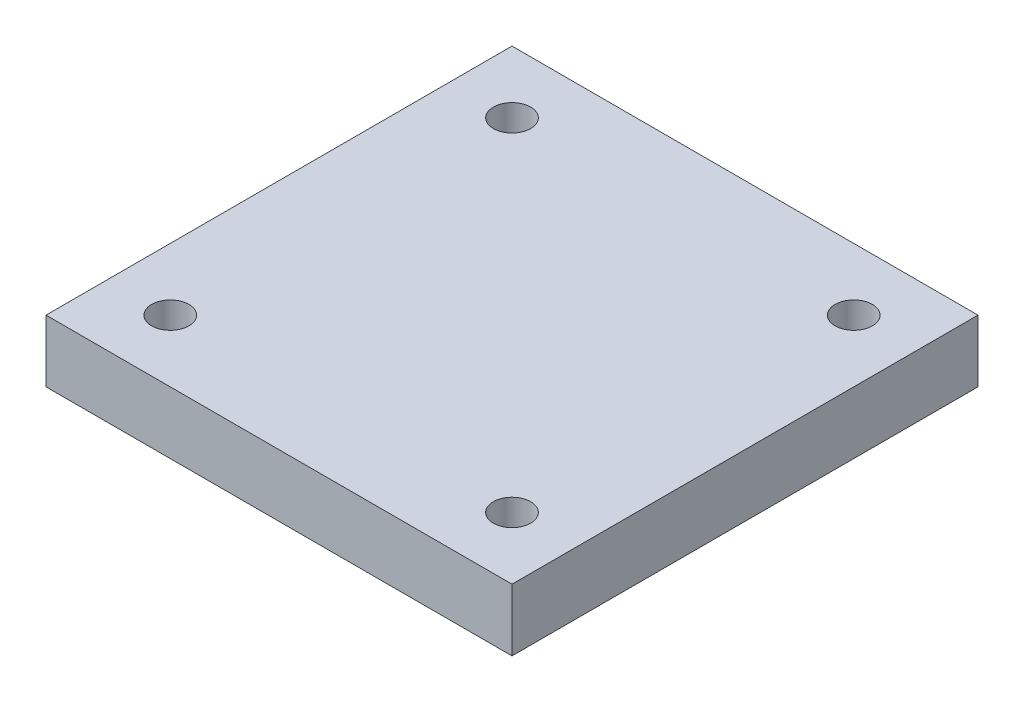
SolidWorks part; units mm, degrees
ref_plane "Front Plane" through (0, 0, 0) normal (0, 0, 1) x (1, 0, 0)
ref_plane "Top Plane" through (0, 0, 0) normal (0, 1, 0) x (1, 0, 0)
ref_plane "Right Plane" through (0, 0, 0) normal (1, 0, 0) x (0, 0, -1)
sketch "Sketch1" plane through (0, 0, 0) normal (0, 1, 0) x (1, 0, 0)
  line L1 (75, 75) -> (-75, 75)
  line L2 (75, 75) -> (75, -75)
  line L3 (75, -75) -> (-75, -75)
  line L4 (-75, 75) -> (-75, -75)
  line L5 (75, 75) -> (-75, -75) construction
  line L6 (75, -75) -> (-75, 75) construction
  point P0 (0, 0)
  dimension "D1" = 150
  dimension "D2" = 150
extrude "Boss-Extrude1" add sketch "Sketch1" along normal blind 20 contours L1 L4 L3 L2
sketch "Sketch2" plane through (0, 20, 0) normal (0, 1, 0) x (1, 0, 0)
  point P0 (55, 55)
  point P1 (55, -55)
  point P2 (-55, -55)
  point P3 (-55, 55)
  point P4 (0, 0)
  point P5 (0, 0)
  point P7 (0, 0)
  point P8 (0, 0)
  point P9 (0, 0)
  point P10 (0, 0)
  point P11 (0, 0)
  dimension "D1" = 110
  dimension "D2" = 55
  dimension "D3" = 55
  dimension "D4" = 55
hole_wizard "Ø12.0mm Dowel Hole1" positions "3DSketch1" profile "Sketch3" hole size "Ø12.0" standard "ANSI Metric" end condition up to next
sketch3d "3DSketch1"
  point P0 (55, 20, -55)
  point P3 (55, 20, 55)
  point P6 (-55, 20, 55)
  point P9 (-55, 20, -55)
sketch "Sketch3" plane through (55, 20, -55) normal (1, 0, 0) x (0, 0, 1)
  line L0 (0, 0) -> (0, 20)
  line L1 (0, 20) -> (6, 20)
  line L2 (6, 20) -> (6, 0)
  line L5 (6, 0) -> (0, 0)
  line L11 (0, -6.35) -> (0, 107.95) construction
  dimension "Thru Hole Dia." = 12
  dimension "Thru Hole Depth" = 20
equation "\"D3@Sketch2\"=\"D1@Sketch2\"/2"
equation "\"D2@Sketch2\"=\"D1@Sketch2\"/2"
equation "\"D4@Sketch2\"=\"D3@Sketch2\""
